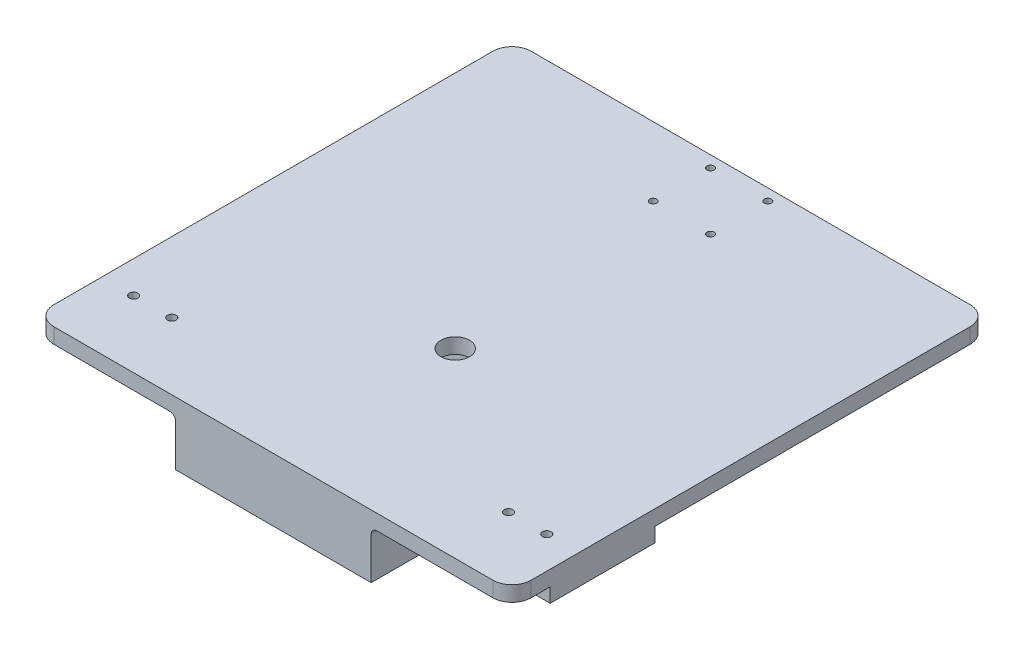
SolidWorks part; units mm, degrees
ref_plane "Front Plane" through (0, 0, 0) normal (0, 0, 1) x (1, 0, 0)
ref_plane "Top Plane" through (0, 0, 0) normal (0, 1, 0) x (1, 0, 0)
ref_plane "Right Plane" through (0, 0, 0) normal (1, 0, 0) x (0, 0, -1)
sketch "Sketch1" plane through (0, 0, 0) normal (0, 1, 0) x (1, 0, 0)
  line L1 (-125, 125) -> (125, 125)
  line L2 (-125, 125) -> (-125, -125)
  line L3 (-125, -125) -> (125, -125)
  line L4 (125, 125) -> (125, -125)
  line L5 (-125, 125) -> (125, -125) construction
  line L6 (-125, -125) -> (125, 125) construction
  point P0 (0, 0)
  dimension "D1" = 250
  dimension "D2" = 250
extrude "Boss-Extrude1" add sketch "Sketch1" along normal blind 8
sketch "Sketch2" plane through (0, 0, 0) normal (0, -1, 0) x (1, 0, 0)
  line L0 (-125, -125) -> (-125, 125) construction
  line L1 (-71.45, 75) -> (-125, 75)
  line L2 (-71.45, 75) -> (-71.45, 105)
  line L3 (-71.45, 105) -> (-125, 105)
  line L4 (-125, 75) -> (-125, 105)
  line L5 (-125, 105) -> (-119, 105) construction
  line L6 (125, 125) -> (125, -125) construction
  line L7 (71.45, 105) -> (125, 105)
  line L8 (71.45, 105) -> (71.45, 50)
  line L9 (71.45, 50) -> (125, 50)
  line L10 (125, 105) -> (125, 50)
extrude "Boss-Extrude2" add sketch "Sketch2" along normal up to surface (7.5 mm away)
sketch "Sketch3" plane through (0, -7.5, 0) normal (0, -1, 0) x (1, 0, 0)
  circle A0 centre (108.225, 90) radius 2.25
  circle A1 centre (88.225, 90) radius 2.25
  circle A2 centre (-108.225, 90) radius 2.25
  circle A3 centre (-88.225, 90) radius 2.25
extrude "Cut-Extrude1" cut sketch "Sketch3" against normal through all
sketch "Sketch4" plane through (0, 0, 0) normal (0, -1, 0) x (1, 0, 0)
  line L0 (0, 125) -> (-51.25, 125)
  line L1 (-48.25, 19.74) -> (0, 19.74) construction
  line L2 (-125, 125) -> (125, 125) construction
  line L3 (0, 122) -> (-48.25, 122) construction
  line L4 (-51.25, 125) -> (-51.25, 16.74)
  line L5 (-51.25, 16.74) -> (0, 16.74)
  line L8 (0, 125) -> (0, -101.2984) construction
  line L9 (-36.25, 112) -> (-36.25, 41.74) construction
  line L10 (-36.25, 41.74) -> (-2.5, 41.74) construction
  line L11 (0, 122) -> (-40.25, 122)
  line L12 (-48.25, 114) -> (-48.25, 27.74)
  line L13 (-40.25, 19.74) -> (0, 19.74)
  line L14 (0, 125) -> (0, -43.5626) construction
  line L15 (40.25, 19.74) -> (0, 19.74)
  line L16 (51.25, 16.74) -> (0, 16.74)
  line L17 (48.25, 114) -> (48.25, 27.74)
  line L18 (0, 122) -> (40.25, 122)
  line L19 (51.25, 125) -> (51.25, 16.74)
  line L20 (0, 125) -> (51.25, 125)
  line L21 (48.25, 70.87) -> (-48.25, 70.87) construction
  line L24 (48.25, 114) -> (40.25, 114)
  line L25 (40.25, 122) -> (40.25, 114)
  line L28 (-48.25, 114) -> (-40.25, 114)
  line L29 (-40.25, 122) -> (-40.25, 114)
  line L32 (-48.25, 27.74) -> (-40.25, 27.74)
  line L33 (-40.25, 19.74) -> (-40.25, 27.74)
  line L36 (48.25, 27.74) -> (40.25, 27.74)
  line L37 (40.25, 19.74) -> (40.25, 27.74)
  line L38 (-48.25, 122) -> (-48.25, 19.74) construction
  circle A0 centre (-44.25, 118) radius 1.5
  circle A1 centre (44.25, 118) radius 1.5
  circle A2 centre (44.25, 23.74) radius 1.5
  circle A3 centre (-44.25, 23.74) radius 1.5
  dimension "D12" = 3
  dimension "D2" = 25
  dimension "D3" = 3
  dimension "D1" = 15
  dimension "D4" = 8
  dimension "D5" = 8
  dimension "D6" = 8
  dimension "D7" = 8
  dimension "D8" = 8
  dimension "D9" = 8
  dimension "D10" = 8
  dimension "D11" = 8
extrude "Boss-Extrude3" add sketch "Sketch4" along normal blind 25
fillet "Fillet1" radius 3 5 edges at (51.25, -12.5, 16.74) (-51.25, -12.5, 16.74) (0, 0, 16.74) (51.25, 0, 70.87) (-51.25, 0, 70.87)
sketch "Sketch5" plane through (-51.25, 0, 0) normal (-1, 0, 0) x (0, 0, 1)
  line L0 (72.37, -3) -> (72.37, -25) construction
  line L1 (125, -3) -> (19.74, -3) construction
  line L2 (125, -25) -> (19.74, -25) construction
  line L4 (82.37, -3) -> (62.37, -3)
  line L5 (82.37, -3) -> (82.37, -13)
  line L6 (82.37, -13) -> (62.37, -13)
  line L7 (62.37, -3) -> (62.37, -13)
  dimension "D1" = 20
  dimension "D2" = 10
  dimension "D3" = 10
extrude "Cut-Extrude2" cut sketch "Sketch5" against normal up to surface (102.5 mm away) up to face at (51.25, -14, 72.37)
sketch "Sketch6" plane through (0, 0, 0) normal (0, -1, 0) x (1, 0, 0)
  line L0 (0, 125) -> (0, -101.2984) construction
  line L1 (-40.25, 19.74) -> (40.25, 19.74) construction
  circle A0 centre (-15, -89) radius 1.851
  circle A1 centre (15, -89) radius 1.851
  circle A2 centre (15, -119) radius 1.851
  circle A3 centre (-15, -119) radius 1.851
  circle A4 centre (0, 29.74) radius 7.5
  dimension "D2" = 15
  dimension "D1" = 10
extrude "Cut-Extrude3" cut sketch "Sketch6" against normal blind 20
fillet "Fillet2" radius 10 4 edges at (-125, 4, -125) (125, 4, -125) (125, 4, 125) (-125, 4, 125)
